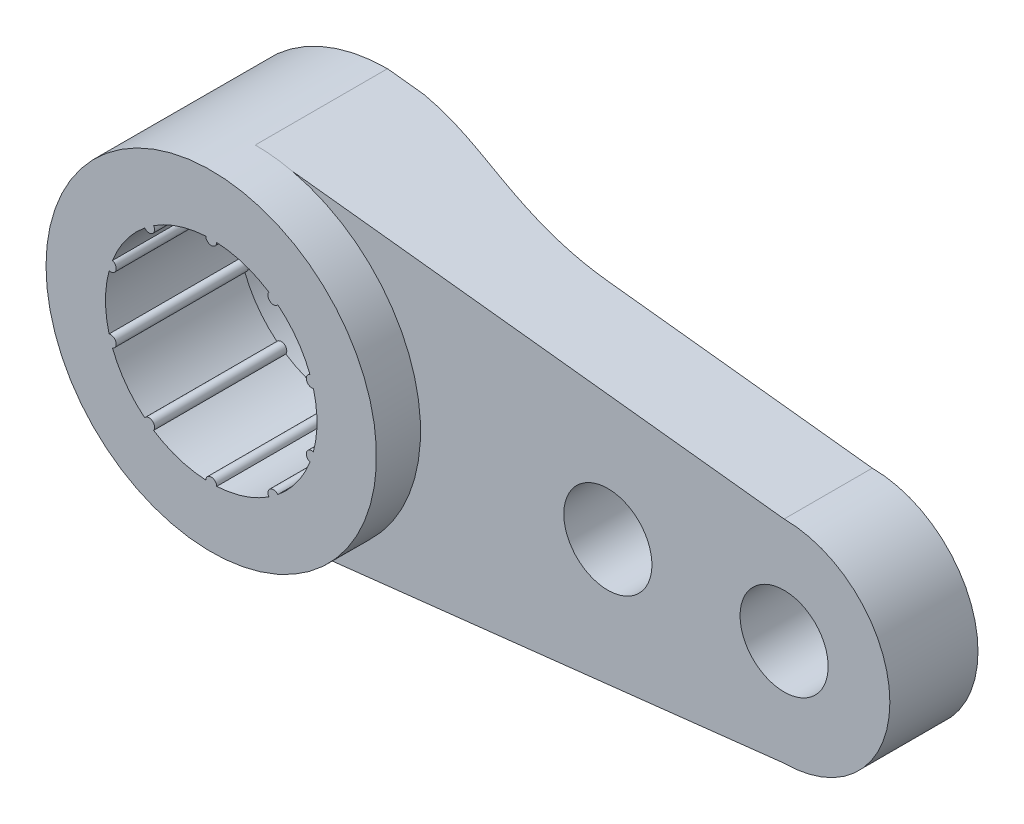
SolidWorks part; units mm, degrees
ref_plane "Front Plane" through (0, 0, 0) normal (0, 0, 1) x (1, 0, 0)
ref_plane "Top Plane" through (0, 0, 0) normal (0, 1, 0) x (1, 0, 0)
ref_plane "Right Plane" through (0, 0, 0) normal (1, 0, 0) x (0, 0, -1)
sketch "Sketch1" plane through (0, 0, 0) normal (0, 0, 1) x (1, 0, 0)
  line L0 (0, 3.75) -> (12, 2.4)
  line L1 (0, -3.75) -> (12, -2.4)
  arc A0 (0.8332, 3.6563) -> (0.8332, -3.6563) centre (0, 0) ccw
  arc A1 (12, -2.4) -> (12, 2.4) centre (12, 0) ccw
  circle A2 centre (0, 0) radius 2.4
  dimension "D1" = 7.5
  dimension "D2" = 4.8
  dimension "D4" = 4.8
  dimension "D3" = 12
extrude "Boss-Extrude1" add sketch "Sketch1" along normal blind 2 contours L1 A1 L0 A0 A2 region at (5.6774, 0, 0)
sketch "Sketch2" plane through (0, 0, 2) normal (0, 0, 1) x (1, 0, 0)
  line L2 (0, -3.75) -> (12, -2.4)
  line L3 (12, 2.4) -> (0, 3.75)
  circle A0 centre (0, 0) radius 2.4 construction
  circle A1 centre (0, 0) radius 2.4
  arc A2 (12, -2.4) -> (12, 2.4) centre (12, 0) ccw
  arc A3 (0, 3.75) -> (0, -3.75) centre (0, 0) ccw
  arc A5 (0, 3.75) -> (0, -3.75) centre (0, 0) ccw
  arc A6 (0, 3.75) -> (0, -3.75) centre (0, 0) cw
  dimension "D1" = 0
extrude "Boss-Extrude2" add sketch "Sketch2" along normal blind 1
sketch "Sketch3" plane through (0, 0, 0) normal (0, 0, -1) x (-1, 0, 0)
  line L2 (-12, -2.4) -> (0, -3.75)
  line L3 (0, 3.75) -> (-12, 2.4)
  circle A0 centre (0, 0) radius 2.4 construction
  circle A1 centre (0, 0) radius 2.4
  arc A2 (0, -3.75) -> (0, 3.75) centre (0, 0) ccw
  arc A3 (-12, 2.4) -> (-12, -2.4) centre (-12, 0) ccw
  arc A4 (0, -3.75) -> (0, 3.75) centre (0, 0) ccw
  circle A6 centre (0, 0) radius 2.75
  arc A7 (0, 3.75) -> (0, -3.75) centre (0, 0) ccw
  line M6 (-12, -2.4) -> (0, -3.75)
  arc M7 (0, -3.75) -> (0, 3.75) centre (0, 0) ccw
  line M8 (0, 3.75) -> (-12, 2.4)
  dimension "D2" = 5.5
  dimension "D1" = 0
extrude "Boss-Extrude3" add sketch "Sketch3" along normal blind 1 contours A7 A6 M8 M6 M7 region at (3.6439, 0, 0)
fillet "Fillet1" radius 5 1 edges at (3.75, 0, 0)
sketch "Sketch4" plane through (0, 0, 0) normal (0, 0, -1) x (-1, 0, 0)
  line L0 (0, 0) -> (-8, 0) construction
  circle A3 centre (-12, 0) radius 1
  circle A4 centre (-8, 0) radius 1
  dimension "D1" = 2
  dimension "D2" = 2
  dimension "D3" = 8
  dimension "D4" = 12
extrude "Cut-Extrude1" cut sketch "Sketch4" against normal up to next
sketch "Sketch5" plane through (0, 0, 0) normal (0, 0, 1) x (1, 0, 0)
  line L0 (0, 0) -> (0, 2.4) construction
  circle A0 centre (0, 0) radius 2.4
  circle A2 centre (0, 2.4) radius 0.125
  circle A3 centre (0, 0) radius 2.4 construction
  point P18 (0, 0)
  dimension "D1" = 0.25
extrude "Boss-Extrude6" add sketch "Sketch5" against normal up to surface (3 mm away) from surface contours A2 L0 A0 | L0 A2 A0 region at (-0.0526, 2.3464, 0) region at (0.0526, 2.3464, 0) up to face at (2.4, 0, 0) starting at face at (-3.75, 0, 3)
pattern_circular "CirPattern1" count 10 over 360 about axis through (0, 0, 2) along (0, 0, -1) of "Boss-Extrude6"
